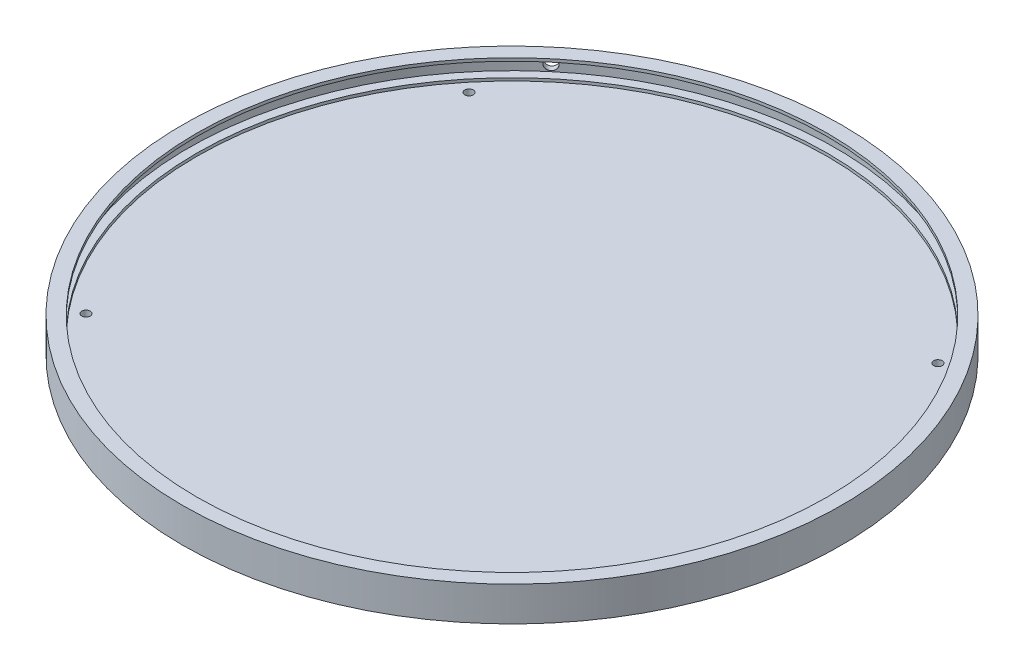
SolidWorks part; units mm, degrees
note: The reader was unsure of these and kept them because the rebuilt part matched: shared geometry of "草图1<8>".
ref_plane "前视基准面" through (0, 0, 0) normal (0, 0, 1) x (1, 0, 0)
ref_plane "上视基准面" through (0, 0, 0) normal (0, 1, 0) x (1, 0, 0)
ref_plane "右视基准面" through (0, 0, 0) normal (1, 0, 0) x (0, 0, -1)
other "Configuration Table"
sketch "草图1" plane through (0, 0, 0) normal (0, 1, 0) x (1, 0, 0)
  circle A0 centre (0, 0) radius 110
  circle A1 centre (0, 0) radius 115
  circle A2 centre (-81.8198, 66.8198) radius 1.5
  circle A3 centre (-81.8198, -66.8198) radius 1.5
  circle A4 centre (83.8198, -66.8198) radius 1.5
  circle A5 centre (81.8198, 66.8198) radius 1.5
  point P5 (0, -110)
  point P32 (0.0184, -69.2688)
extrude "凸台-拉伸3" add sketch "草图1" along normal blind 12.0333
extrude "凸台-拉伸4" add sketch "草图1<8>" along normal blind 5
sketch "草图1<8>" plane through (0, 0, 0) normal (0, 1, 0) x (1, 0, 0) same geometry as "草图1"
sketch "草图4" plane through (0, 0, 0) normal (0, 1, 0) x (1, 0, 0)
  circle A0 centre (0, 0) radius 113
extrude "切除-拉伸2" cut sketch "草图4" along normal blind 5 from offset 6
sketch "草图14" plane through (0, 0, 0) normal (1, 0, 0) x (0, 0, -1)
  line L0 (73.904, 0) -> (73.904, 6.0166)
  line L1 (-115, 0) -> (115, 0) construction
curve "曲线1"
hole_wizard "Ø4.0mm 暗销孔2" positions "3D草图8" profile "草图19" hole size "Ø4.0" standard "ISO" end condition through all
sketch3d "3D草图8"
  point P2 (-72.8154, 8.2981, -86.4113)
sketch "草图19" plane through (-72.8154, 8.2981, -86.4113) normal (0, 1, 0) x (0.7647, 0, -0.6444)
  line L0 (0, 0) -> (0, 49.0449)
  line L1 (0, 49.0449) -> (2, 49.0449)
  line L2 (2, 49.0449) -> (2, 0.025)
  line L3 (2, 0.025) -> (2.025, 0)
  line L5 (2.025, 0) -> (0, 0)
  line L6 (-2, 0.025) -> (-2.025, 0) construction
  line L11 (0, -6.35) -> (0, 107.95) construction
  dimension "通孔孔直径" = 4
  dimension "通孔孔深度" = 49.0449
  dimension "近端锥形沉头孔直径" = 4.05
  dimension "近端锥形沉头孔角度" = 90
hole_wizard "Ø3.0mm 暗销孔1" positions "3D草图2" profile "草图12" hole size "Ø3.0" standard "ISO"
sketch3d "3D草图2"
  point P0 (-32.0046, 7.9009, 42.2458)
sketch "草图12" plane through (-32.0046, 7.9009, 42.2458) normal (0, 1, 0) x (-0.7971, 0, -0.6039)
  line L0 (0, 0) -> (0, 24.0523)
  line L1 (0, 24.0523) -> (1.5, 24.0523)
  line L2 (1.5, 24.0523) -> (1.5, 0.025)
  line L3 (1.5, 0.025) -> (1.525, 0)
  line L5 (1.525, 0) -> (0, 0)
  line L6 (-1.5, 0.025) -> (-1.525, 0) construction
  line L11 (0, -6.35) -> (0, 107.95) construction
  dimension "通孔孔直径" = 3
  dimension "通孔孔深度" = 24.0523
  dimension "近端锥形沉头孔直径" = 3.05
  dimension "近端锥形沉头孔角度" = 90
sketch "草图13" plane through (0, 0, 0) normal (0, 1, 0) x (1, 0, 0)
  line L0 (-31.8198, -31.8198) -> (31.8198, -31.8198) construction
  line L5 (31.8198, -31.8198) -> (36.8198, -31.8198)
  line L6 (-31.8198, -31.8198) -> (-36.8198, -31.8198)
  line L7 (24.6728, -26.308) -> (24.6728, -99.3111)
  line L8 (37.8128, -26.308) -> (-37.8128, -26.308)
  line L9 (37.8128, -26.308) -> (37.8128, -37.3316)
  line L10 (37.8128, -37.3316) -> (-37.8128, -37.3316)
  line L11 (-37.8128, -26.308) -> (-37.8128, -37.3316)
  line L12 (0, -37.3316) -> (0, -26.308) construction
  line L13 (37.8128, -31.8198) -> (-37.8128, -31.8198) construction
  line L16 (24.6728, -99.3111) -> (-24.6728, -99.3111) construction
  line L18 (0, -80.4047) -> (0, -98.3189) construction
  line L19 (24.6728, -31.8198) -> (-24.6728, -31.8198) construction
  line L20 (24.6728, -99.3111) -> (-24.6728, -99.3111)
  line L21 (-24.6728, -99.3111) -> (-24.6728, -26.308)
  line L22 (-24.6728, -26.308) -> (24.6728, -26.308)
  line L23 (25.7634, -90.4047) -> (-32.1141, -90.4047) construction
  circle A0 centre (0, -90.4047) radius 3
  circle A1 centre (-14.9497, -85.455) radius 1.5
  circle A2 centre (-4.9497, -85.455) radius 1.5
  circle A3 centre (4.9497, -85.455) radius 1.5
  circle A4 centre (-4.9497, -95.3545) radius 1.5
  circle A5 centre (4.9497, -95.3545) radius 1.5
  circle A6 centre (-14.9497, -95.3545) radius 1.5
  circle A7 centre (14.9497, -85.455) radius 1.5
  circle A8 centre (14.9497, -95.3545) radius 1.5
  point P4 (0, -31.8198)
  point P10 (0, -31.8198)
  point P28 (0, -90.4047)
